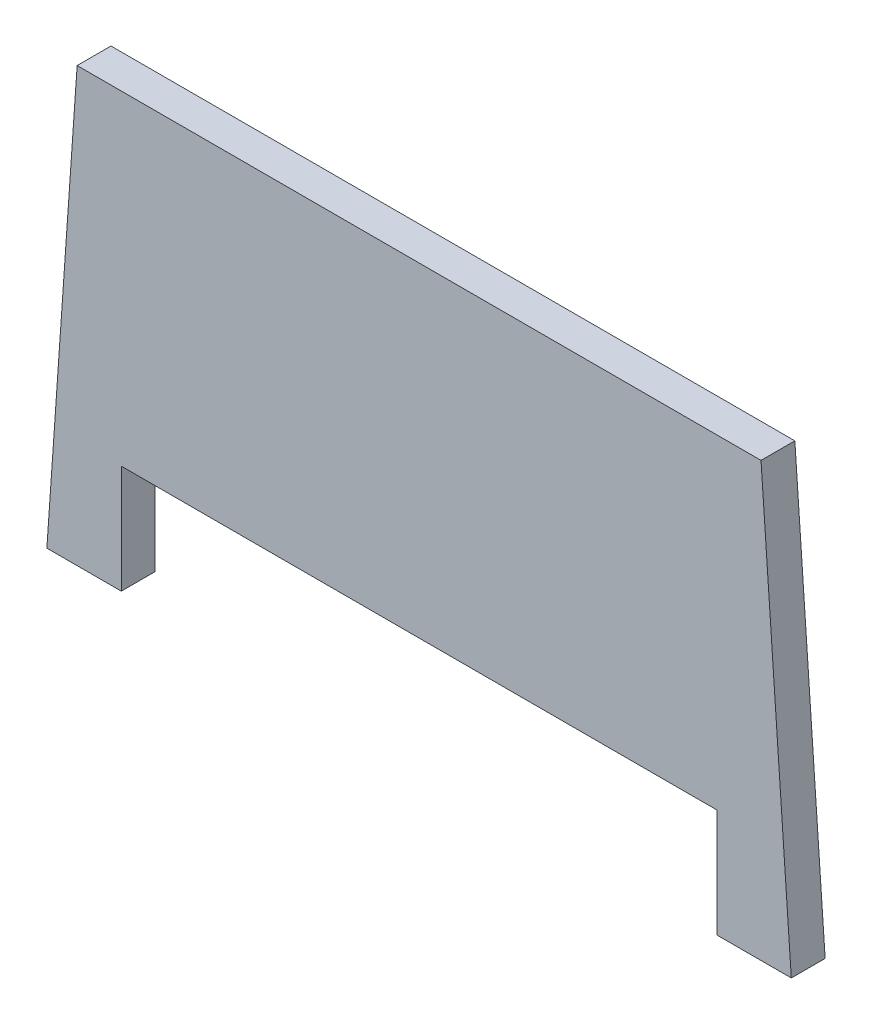
SolidWorks part; units mm, degrees
ref_plane "Front Plane" through (0, 0, 0) normal (0, 0, 1) x (1, 0, 0)
ref_plane "Top Plane" through (0, 0, 0) normal (0, 1, 0) x (1, 0, 0)
ref_plane "Right Plane" through (0, 0, 0) normal (1, 0, 0) x (0, 0, -1)
sketch "Sketch1" plane through (0, 0, 0) normal (0, 0, 1) x (1, 0, 0)
  line L0 (50, 0) -> (185, 0)
  line L1 (185, 0) -> (185, 80)
  line L2 (185, 80) -> (465, 80)
  line L3 (465, 80) -> (465, 0)
  line L4 (465, 0) -> (600, 0)
  line L5 (650, 0) -> (627.6234, 320) construction
  line L6 (577.6234, 320) -> (72.3766, 320)
  line L7 (22.3766, 320) -> (0, 0) construction
  line L8 (0, 0) -> (0, 38.1344) construction
  line L9 (650, 0) -> (650, 152.4204) construction
  line L10 (50, 0) -> (72.3766, 320)
  line L11 (600, 0) -> (577.6234, 320)
  line L12 (22.3766, 320) -> (72.3766, 320) construction
  line L13 (0, 0) -> (50, 0) construction
  line L14 (627.6234, 320) -> (577.6234, 320) construction
  line L15 (600, 0) -> (650, 0)
  dimension "D1" = 4
  dimension "D2" = 4
  dimension "D3" = 650
  dimension "D4" = 80
  dimension "D5" = 320
  dimension "D6" = 280
  dimension "D7" = 50
  dimension "D8" = 50
  dimension "D9" = 185
extrude "Boss-Extrude1" add sketch "Sketch1" along normal blind 25 contours L10 L0 L1 L2 L3 L4 L11 L6
sketch "Sketch3" plane through (0, 0, 25) normal (0, 0, 1) x (1, 0, 0)
  line L0 (50, 0) -> (185, 0) construction
  line L1 (185, 80) -> (105, 80)
  line L2 (185, 80) -> (185, 0)
  line L3 (185, 0) -> (105, 0)
  line L4 (105, 80) -> (105, 0)
  line L5 (465, 0) -> (600, 0) construction
  line L6 (465, 80) -> (545, 80)
  line L7 (465, 80) -> (465, 0)
  line L8 (465, 0) -> (545, 0)
  line L9 (545, 80) -> (545, 0)
  dimension "D1" = 80
  dimension "D2" = 80
extrude "Cut-Extrude2" cut sketch "Sketch3" against normal through all
sketch "Sketch2" plane through (0, 0, 25) normal (0, 0, 1) x (1, 0, 0)
  line L0 (50, 0) -> (105, 0) construction
  line L1 (545, 0) -> (600, 0) construction
  circle A0 centre (145, 33) radius 20
  circle A1 centre (505, 33) radius 20
  dimension "D1" = 145
  dimension "D2" = 40
  dimension "D4" = 360
  dimension "D6" = 40
  dimension "D3" = 33
  dimension "D5" = 33
